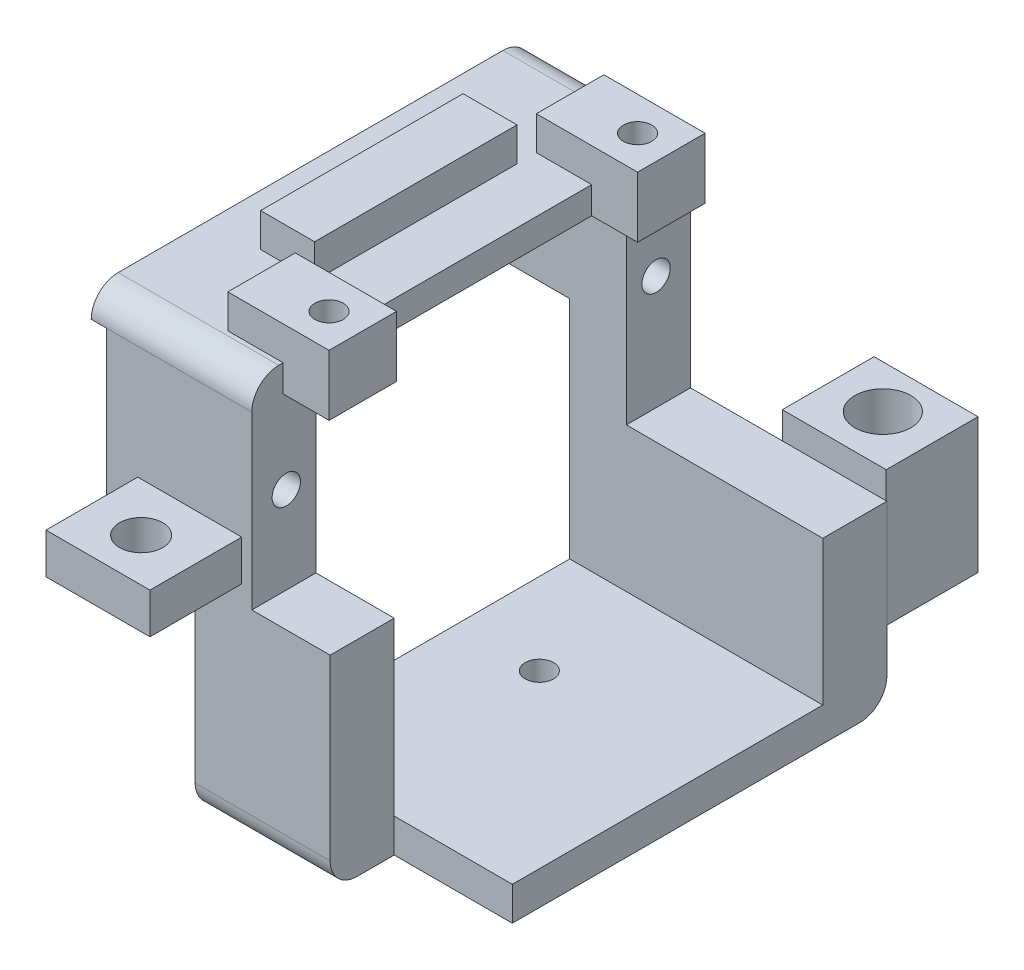
SolidWorks part; units mm, degrees
ref_plane "Front Plane" through (0, 0, 0) normal (0, 0, 1) x (1, 0, 0)
ref_plane "Top Plane" through (0, 0, 0) normal (0, 1, 0) x (1, 0, 0)
ref_plane "Right Plane" through (0, 0, 0) normal (1, 0, 0) x (0, 0, -1)
sketch "Sketch1" plane through (0, 0, 0) normal (0, 1, 0) x (1, 0, 0)
  line L0 (-1.1, 16.25) -> (-1.1, 11.5)
  line L1 (-17.65, -16.25) -> (17.65, -16.25)
  line L2 (-17.65, -16.25) -> (-17.65, 16.25)
  line L3 (-17.65, 16.25) -> (17.65, 16.25)
  line L4 (17.65, -16.25) -> (17.65, 16.25)
  line L5 (-17.65, -16.25) -> (17.65, 16.25) construction
  line L6 (-17.65, 16.25) -> (17.65, -16.25) construction
  line L7 (-1.1, 11.5) -> (17.65, 11.5)
  line L8 (-1.1, -16.25) -> (-1.1, -11.5)
  line L9 (-1.1, -11.5) -> (17.65, -11.5)
  line L10 (-1.1, 11.5) -> (-1.1, -11.5) construction
  line L11 (8.9, -11.5) -> (8.9, -16.25)
  line L12 (-8.8, 16.25) -> (-8.8, 11.5)
  line L13 (-8.8, 11.5) -> (-3.8, 11.5)
  line L14 (-3.8, 11.5) -> (-3.8, 16.25)
  line L15 (-3.8, -16.25) -> (-3.8, -11.5)
  line L16 (-3.8, -11.5) -> (-8.8, -11.5)
  line L17 (-8.8, -11.5) -> (-8.8, -16.25)
  line L18 (-8.8, 11.5) -> (-8.8, -11.5)
  line L19 (17.6, 16.25) -> (17.6, 23.05)
  line L20 (17.6, 23.05) -> (9.9, 23.05)
  line L21 (9.9, 23.05) -> (9.9, 16.25)
  line L22 (-5.35, -16.25) -> (-5.35, -23.05)
  line L23 (-5.35, -23.05) -> (2.35, -23.05)
  line L24 (2.35, -23.05) -> (2.35, -16.25)
  line L28 (-1.1, 11.5) -> (-1.1, -11.5)
  circle A0 centre (13.75, 19.85) radius 2.075
  circle A2 centre (-1.5, -19.85) radius 1.6
  point P0 (0, 0)
  point P11 (-1.1, 0)
  point P31 (13.75, 23.05)
  point P45 (-1.5, -23.05)
  dimension "D11" = 4.15
  dimension "D19" = 3.2
  dimension "D1" = 32.5
  dimension "D2" = 23
  dimension "D3" = 8.75
  dimension "D4" = 10
  dimension "D5" = 16.55
  dimension "D6" = 2.7
  dimension "D7" = 5
  dimension "D8" = 13.75
  dimension "D9" = 7.7
  dimension "D10" = 6.8
  dimension "D12" = 1.5
  dimension "D13" = 19.85
  dimension "D16" = 7.7
  dimension "D17" = 6.8
  dimension "D20" = 19.85
extrude "Boss-Extrude1" add sketch "Sketch1" against normal blind 2.5 contours L7 L28 L9 L4 | L0 L7 L4 L3 | L11 L9 L8 L1 region at (8.275, 0, -13.875) region at (8.275, 0, 0) region at (3.9, 0, 13.875)
extrude "Boss-Extrude2" add sketch "Sketch1<3>" along normal blind 12.7 contours L0 L7 L4 L3 | L11 L9 L8 L1 region at (8.275, 0, -13.875) region at (3.9, 0, 13.875)
sketch "Sketch1<3>" plane through (0, 0, 0) normal (0, 1, 0) x (1, 0, 0) same geometry as "Sketch1"
sketch "Sketch3" plane through (0, 0, 0) normal (0, 1, 0) x (1, 0, 0)
  line L0 (3.1, 16.25) -> (3.1, 11.5)
  line L1 (-17.65, 16.25) -> (17.65, 16.25) construction
  line L2 (-1.1, 11.5) -> (17.65, 11.5) construction
  line L3 (3.1, 11.5) -> (-17.65, 11.5)
  line L4 (-17.65, -16.25) -> (-17.65, 16.25) construction
  line L5 (3.1, -16.25) -> (3.1, -11.5)
  line L6 (-17.65, -16.25) -> (17.65, -16.25) construction
  line L7 (-1.1, -11.5) -> (17.65, -11.5) construction
  line L8 (3.1, -11.5) -> (-17.65, -11.5)
  line L9 (3.1, 11.5) -> (3.1, -11.5)
  line L10 (-7.65, -11.5) -> (-7.65, -16.275)
  line L11 (3.1, 16.25) -> (-17.65, 16.25)
  line L12 (-17.65, 16.25) -> (-17.65, 11.5)
  line L13 (-17.65, -11.5) -> (-17.65, -16.25)
  line L14 (-17.65, -16.25) -> (3.1, -16.25)
  line L15 (-8.8, 11.5) -> (-8.8, -11.5)
  line L16 (-8.8, 11.5) -> (-8.8, 16.25)
  line L17 (-8.8, -11.5) -> (-8.8, -16.25)
  dimension "D1" = 20.75
  dimension "D2" = 10
extrude "Boss-Extrude3" add sketch "Sketch3" along normal blind 12.7 from surface contours L11 L12 L3 L0 | L10 L14 L5 L8 region at (-2.85, 0, -13.875) region at (-2.275, 0, 13.875) starting at face at (8.275, 12.7, -13.875)
extrude "Boss-Extrude4" add sketch "Sketch3<3>" along normal blind 2 from surface contours L16 L3 L0 L11 | L3 L15 L8 L9 | L10 L14 L5 L8 | L8 L17 L14 L10 region at (-2.85, 0, -13.875) region at (-2.85, 0, 0) region at (-2.275, 0, 13.875) region at (-8.225, 0, 13.875) starting at face at (-2.275, 25.4, 13.875)
sketch "Sketch3<3>" plane through (0, 0, 0) normal (0, 1, 0) x (1, 0, 0) same geometry as "Sketch3"
sketch "Sketch2" plane through (0, 0, 0) normal (1, 0, 0) x (0, 0, -1)
  line L0 (13.7, 6.45) -> (-13.7, 6.45) construction
  line L1 (-13.7, 19.15) -> (13.7, 19.15) construction
  circle A0 centre (13.7, 6.45) radius 1.05
  circle A1 centre (-13.7, 6.45) radius 1.05
  circle A2 centre (-13.7, 19.15) radius 1.05
  circle A3 centre (13.7, 19.15) radius 1.05
  point P4 (0, 6.45)
  dimension "D1" = 2.1
  dimension "D2" = 2.1
  dimension "D6" = 2.1
  dimension "D7" = 2.1
  dimension "D3" = 27.4
  dimension "D4" = 6.45
  dimension "D5" = 6.45
extrude "Cut-Extrude1" cut sketch "Sketch2" along normal blind 8 from surface contours A1 | A0 region at (0, 6.45, -13.7) region at (0, 6.45, 13.7) starting at face at (-1.1, 5.725, 0)
extrude "Cut-Extrude2" cut sketch "Sketch2<3>" against normal blind 8 from surface contours A3 | A2 region at (0, 19.15, 13.7) region at (0, 19.15, -13.7) starting at face at (3.1, 19.55, 0)
sketch "Sketch2<3>" plane through (0, 0, 0) normal (1, 0, 0) x (0, 0, -1) same geometry as "Sketch2"
extrude "Boss-Extrude5" add sketch "Sketch1<4>" against normal blind 3 from offset 17 contours L23 L24 L1 L22 A2 region at (0.625, 0, 16.3527)
sketch "Sketch1<4>" plane through (0, 0, 0) normal (0, 1, 0) x (1, 0, 0) same geometry as "Sketch1"
extrude "Boss-Extrude6" add sketch "Sketch1<7>" against normal blind 10 from surface contours L20 L21 L3 L19 A0 region at (10.0027, 0, -19.65) starting at face at (10.375, 12.7, -13.875)
sketch "Sketch1<7>" plane through (0, 0, 0) normal (0, 1, 0) x (1, 0, 0) same geometry as "Sketch1"
fillet "Fillet1" radius 2 4 edges at (3.9, -2.5, 16.25) (-2.85, 27.4, 16.25) (8.275, -2.5, -16.25) (-2.85, 27.4, -16.25)
sketch "Sketch5" plane through (0, 0, 0) normal (0, 1, 0) x (1, 0, 0)
  line L1 (17.65, 16.25) -> (3.1, 16.25)
  line L2 (17.65, 16.25) -> (17.65, 11.5)
  line L3 (17.65, 11.5) -> (3.1, 11.5)
  line L4 (3.1, 16.25) -> (3.1, 11.5)
extrude "Cut-Extrude3" cut sketch "Sketch5" against normal blind 2 from surface starting at face at (12.0625, 12.7, -16.7625)
sketch "Sketch6" plane through (0, 0, 0) normal (0, 1, 0) x (1, 0, 0)
  line L1 (-8.8, 11.5) -> (-1.1, 11.5)
  line L2 (-8.8, 11.5) -> (-8.8, 16.25)
  line L3 (-8.8, 16.25) -> (-1.1, 16.25)
  line L4 (-1.1, 11.5) -> (-1.1, 16.25)
extrude "Cut-Extrude4" cut sketch "Sketch6" along normal blind 4 from surface starting at face at (-4.95, 12.7, -13.875)
sketch "Sketch7" plane through (0, 0, 0) normal (0, 1, 0) x (1, 0, 0)
  line L0 (4, 11.43) -> (4, -11.43) construction
  line L2 (1.5, 13.93) -> (6.5, 13.93)
  line L3 (1.5, 13.93) -> (1.5, 8.93)
  line L4 (1.5, 8.93) -> (6.5, 8.93)
  line L5 (6.5, 13.93) -> (6.5, 8.93)
  line L6 (1.5, 13.93) -> (6.5, 8.93) construction
  line L7 (1.5, 8.93) -> (6.5, 13.93) construction
  line L8 (1.5, -8.93) -> (6.5, -8.93)
  line L9 (1.5, -8.93) -> (1.5, -13.93)
  line L10 (1.5, -13.93) -> (6.5, -13.93)
  line L11 (6.5, -8.93) -> (6.5, -13.93)
  line L12 (1.5, -8.93) -> (6.5, -13.93) construction
  line L13 (1.5, -13.93) -> (6.5, -8.93) construction
  line L21 (-5, -7.5) -> (-1, -7.5)
  line L22 (-5, -7.5) -> (-5, 7.5)
  line L23 (-5, 7.5) -> (-1, 7.5)
  line L24 (-1, -7.5) -> (-1, 7.5)
  line L25 (-5, -7.5) -> (-1, 7.5) construction
  line L26 (-5, 7.5) -> (-1, -7.5) construction
  line L27 (1.5, 13.93) -> (-1, 13.93)
  line L28 (1.5, 13.93) -> (1.5, 8.93)
  line L29 (1.5, 8.93) -> (-1, 8.93)
  line L30 (-1, 13.93) -> (-1, 8.93)
  line L31 (1.5, -13.93) -> (-1, -13.93)
  line L32 (1.5, -13.93) -> (1.5, -8.93)
  line L33 (1.5, -8.93) -> (-1, -8.93)
  line L34 (-1, -13.93) -> (-1, -8.93)
  circle A0 centre (4, 11.43) radius 1.05
  circle A1 centre (4, -11.43) radius 1.05
  point P4 (4, 0)
  point P14 (-3, 0)
  dimension "D1" = 2.1
  dimension "D2" = 2.1
  dimension "D3" = 22.86
  dimension "D4" = 5
  dimension "D5" = 5
  dimension "D6" = 5
  dimension "D7" = 5
  dimension "D8" = 4
  dimension "D9" = 3
  dimension "D10" = 15
  dimension "D11" = 4
extrude "Boss-Extrude7" add sketch "Sketch7" along normal blind 2.5 and the other way blind 2 from surface contours L21 L24 L23 L22 | L11 L8 L9 L10 A1 | L34 L31 L9 L33 | L27 L30 L29 L3 | L5 L2 L3 L4 A0 region at (4, 0, -13.8593) region at (0.25, 0, -11.43) region at (4, 0, 9.0007) region at (0.25, 0, 11.43) region at (-3, 0, 0) starting at face at (-2.85, 27.4, 0)
sketch "Sketch8" plane through (0, 0, 0) normal (0, 1, 0) x (1, 0, 0)
  line L2 (-17.65, -16.25) -> (17.65, -16.25) construction
  line L3 (7.45, 5.7) -> (2.45, 5.7)
  line L4 (7.45, 5.7) -> (7.45, 0.7)
  line L5 (7.45, 0.7) -> (2.45, 0.7)
  line L6 (2.45, 5.7) -> (2.45, 0.7)
  line L7 (7.45, 5.7) -> (2.45, 0.7) construction
  line L8 (7.45, 0.7) -> (2.45, 5.7) construction
  line L11 (-1.1, 11.5) -> (-1.1, -11.5) construction
  circle A0 centre (4.95, 3.2) radius 1.05
  dimension "D3" = 2.1
  dimension "D1" = 6.05
  dimension "D2" = 19.45
  dimension "D4" = 5
  dimension "D5" = 5
extrude "Boss-Extrude8" add sketch "Sketch8" against normal blind 4.1 from surface starting at face at (8.4833, -2.5, 3.8333)
extrude "Cut-Extrude5" cut sketch "Sketch8<2>" against normal through all both contours A0 region at (4.95, 0, -3.2)
sketch "Sketch8<2>" plane through (0, 0, 0) normal (0, 1, 0) x (1, 0, 0) same geometry as "Sketch8"
extrude "Cut-Extrude6" cut sketch "Sketch7<4>" along normal up to surface (29.9 mm away) from surface contours A0 | A1 region at (4, 0, -11.43) region at (4, 0, 11.43) up to face at (4, 29.9, 10.38) starting at face at (1.5556, 25.4, 1.8056)
sketch "Sketch7<4>" plane through (0, 0, 0) normal (0, 1, 0) x (1, 0, 0) same geometry as "Sketch7"
